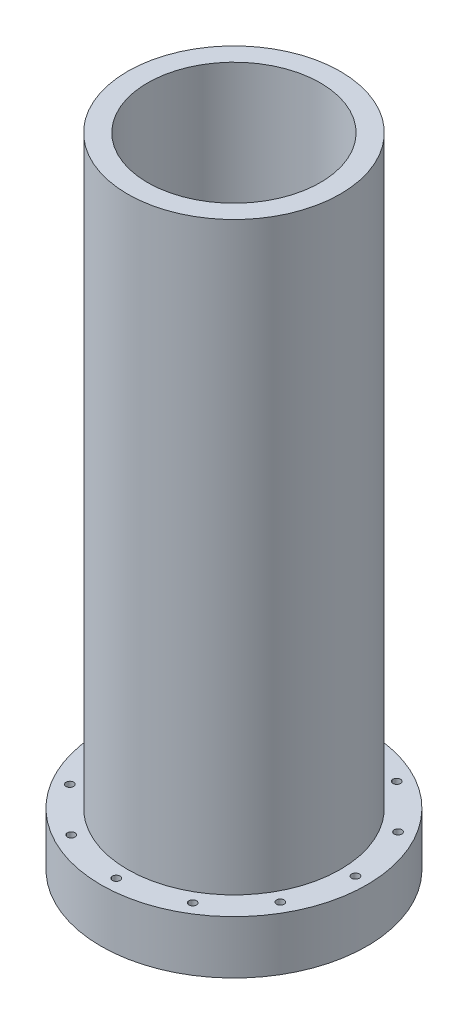
SolidWorks part; units mm, degrees
ref_plane "Front Plane" through (0, 0, 0) normal (0, 0, 1) x (1, 0, 0)
ref_plane "Top Plane" through (0, 0, 0) normal (0, 1, 0) x (1, 0, 0)
ref_plane "Right Plane" through (0, 0, 0) normal (1, 0, 0) x (0, 0, -1)
sketch "Sketch2" plane through (0, 0, 0) normal (0, 1, 0) x (1, 0, 0)
  circle A0 centre (0, 0) radius 41.275
  circle A1 centre (0, 0) radius 50.8
  dimension "D1" = 101.6
  dimension "D2" = 82.55
extrude "Boss-Extrude1" add sketch "Sketch2" along normal blind 304.8
sketch "Sketch4" plane through (0, 0, 0) normal (0, 1, 0) x (1, 0, 0)
  circle A0 centre (0, 0) radius 63.5
  circle A1 centre (0, 0) radius 44.45
  dimension "D1" = 127
extrude "Boss-Extrude3" add sketch "Sketch4" along normal blind 25.4
sketch "Sketch5" plane through (0, 25.4, 0) normal (0, 1, 0) x (1, 0, 0)
  circle A0 centre (29.354, -49.0353) radius 1.8147
  circle A1 centre (0, 0) radius 63.5 construction
  circle A2 centre (0.9037, -57.1429) radius 1.8147
  circle A3 centre (-27.7888, -49.939) radius 1.8147
  circle A4 centre (-49.0353, -29.354) radius 1.8147
  circle A5 centre (-57.1429, -0.9037) radius 1.8147
  circle A6 centre (-49.939, 27.7888) radius 1.8147
  circle A7 centre (-29.354, 49.0353) radius 1.8147
  circle A8 centre (-0.9037, 57.1429) radius 1.8147
  circle A9 centre (27.7888, 49.939) radius 1.8147
  circle A10 centre (49.0353, 29.354) radius 1.8147
  circle A11 centre (57.1429, 0.9037) radius 1.8147
  circle A12 centre (49.939, -27.7888) radius 1.8147
  point P28 (0, 0)
  dimension "D1" = 57.15
  dimension "D2" = 12
extrude "Cut-Extrude1" cut sketch "Sketch5" against normal through all both and the other way through all
